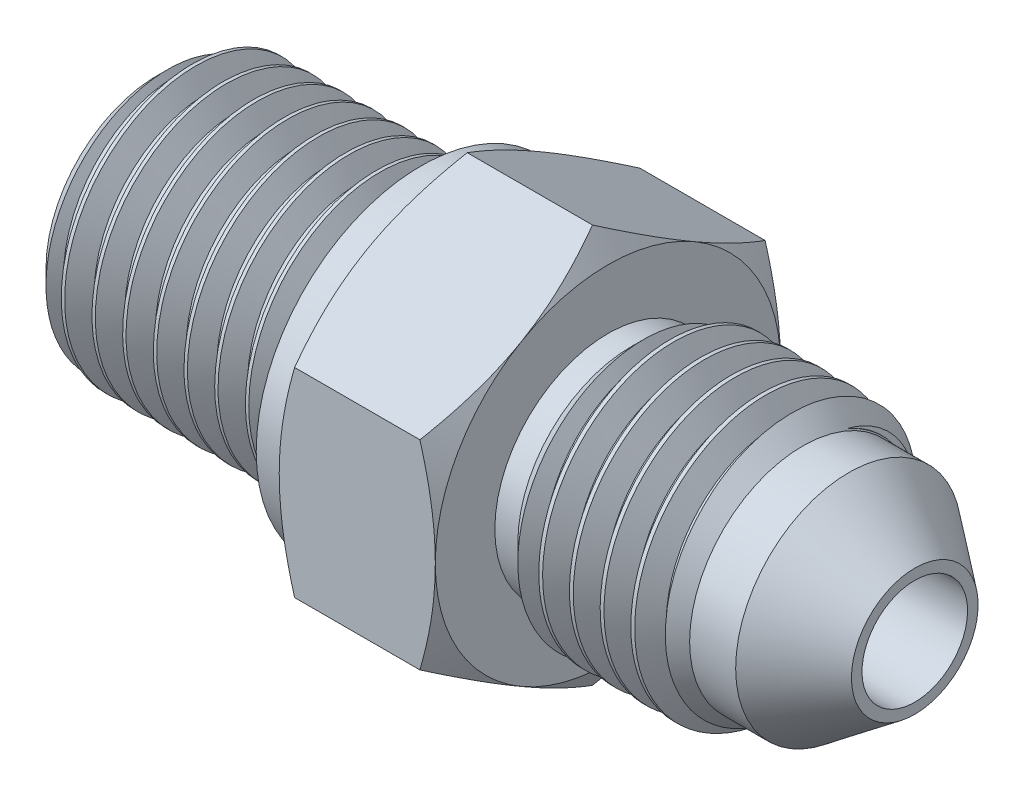
SolidWorks part; units mm, degrees
ref_plane "Front" through (0, 0, 0) normal (0, 0, 1) x (1, 0, 0)
ref_plane "Top" through (0, 0, 0) normal (0, 1, 0) x (1, 0, 0)
ref_plane "Right" through (0, 0, 0) normal (1, 0, 0) x (0, 0, -1)
sketch "Sketch6" plane through (0, 0, 0) normal (0, 0, 1) x (1, 0, 0)
  line L0 (-3.4836, 5.5562) -> (-3.4836, -5.5562) construction
  line L1 (15.6756, 5.5562) -> (15.6756, -5.5563) construction
  line L2 (-15.6756, 0) -> (15.6756, 0)
  line L4 (-15.6756, 0) -> (-15.6756, 5.5563)
  line L5 (-15.6756, 5.5563) -> (15.6756, 5.5562)
  line L6 (15.6756, 0) -> (15.6756, 5.5562)
  point P4 (2.9756, 0)
  point P6 (-3.4836, 0)
  dimension "Straight Dia" = 11.1125
  dimension "Length" = 31.3512
  dimension "L1" = 12.7
  dimension "Pipe OD" = 11.1125
  dimension "Pipe Thread Length" = 12.192
revolve "Revolve3" add sketch "Sketch6" angle 360 about L2
sketch "Sketch14" plane through (15.6756, 0, 0) normal (-1, 0, 0) x (0, 0, 1)
  circle A1 centre (0, 0) radius 5.5563
  circle A2 centre (0, 0) radius 5.5563
  dimension "D1" = 0
curve "Helix/Spiral1" pitch 1.27 height 13.97 turns 11 parameters "Pitch"=1.27
sketch "Sketch15" plane through (0, 0, 0) normal (0, 0, 1) x (1, 0, 0)
  line L0 (15.6756, 5.5563) -> (16.7869, 5.5562)
  line L1 (16.7869, 5.5562) -> (16.3106, 4.7314)
  line L2 (16.3106, 4.7314) -> (16.1519, 4.7314)
  line L3 (16.1519, 4.7314) -> (15.6756, 5.5563)
  line L4 (16.2312, 4.7314) -> (16.2312, 5.5563) construction
  line L5 (15.9137, 5.1438) -> (16.5487, 5.1438) construction
  dimension "D1" = 60
  dimension "D2" = 0.1588
  dimension "D3" = 0.635
sweep "Cut-Sweep1" cut profiles "Sketch15" path "Helix/Spiral1" align with end faces yes
ref_plane "Plane1" through (-3.4836, 0, 0) normal (1, 0, 0) x (0, 0, -1)
sketch "Sketch12" plane through (-3.4836, 0, 0) normal (1, 0, 0) x (0, 0, -1)
  line L1 (0, 8.2489) -> (-7.1437, 4.1244)
  line L2 (-7.1437, 4.1244) -> (-7.1437, -4.1244)
  line L3 (-7.1437, -4.1244) -> (0, -8.2489)
  line L4 (0, -8.2489) -> (7.1438, -4.1244)
  line L5 (7.1438, -4.1244) -> (7.1437, 4.1244)
  line L6 (7.1437, 4.1244) -> (0, 8.2489)
  circle A0 centre (0, 0) radius 7.1438 construction
  dimension "Hex" = 14.2875
extrude "Extrude1" add sketch "Sketch12" along normal up to vertex (6.4592 mm away) up to point (2.9756, 0, 0)
sketch "Sketch7" plane through (0, 0, 0) normal (0, 0, 1) x (1, 0, 0)
  line L0 (-15.6756, 0) -> (-15.6756, 2.1844)
  line L2 (-15.6756, 2.1844) -> (15.6756, 2.1844)
  line L4 (15.6756, 0) -> (15.6756, 5.5562) construction
  line L11 (15.6756, 2.1844) -> (15.6756, 0)
  line L12 (15.6756, 0) -> (-15.6756, 0)
  line L13 (-15.6756, 2.1844) -> (-15.6756, -2.1844) construction
  dimension "ID" = 4.3688
sketch "Sketch10" plane through (0, 0, 0) normal (0, 0, 1) x (1, 0, 0)
  line L0 (-15.6756, 5.5563) -> (15.6756, 5.5562) construction
  line L1 (15.6756, 5.5563) -> (16.7869, 5.5562) construction
  line L3 (2.9756, 8.2489) -> (2.9756, 4.1244) construction
  line L5 (0, 0) -> (-15.6756, 0) construction
  line L6 (4.8038, 5.5562) -> (2.9756, 5.5562)
  line L9 (2.9756, 4.6806) -> (2.9756, 5.5562)
  line L21 (15.6756, 5.5563) -> (10.1622, 5.5562)
  line L22 (10.1622, 5.5562) -> (11.0379, 4.6806)
  line L23 (11.0379, 4.6806) -> (12.9429, 4.6806)
  line L24 (12.9429, 4.6806) -> (15.6756, 2.6213)
  line L25 (15.6756, 2.6213) -> (15.6756, 5.5563)
  line L26 (3.9281, 4.6806) -> (2.9756, 4.6806)
  line L27 (4.8038, 5.5562) -> (3.9281, 4.6806)
  point P5 (8.4979, -5.5563)
  point P9 (-10.4026, -7.1438)
  point P24 (-10.4026, 0)
  dimension "D1" = 5.2426
  dimension "D2" = 37
  dimension "D3" = 1.905
  dimension "D5" = 45
  dimension "D4" = 0.9525
  dimension "D6" = 2.54
  dimension "D7" = 0.0508
revolve "Cut-Revolve6" cut sketch "Sketch10" angle 360 about L2
revolve "Cut-Revolve5" cut sketch "Sketch7" angle 360 about L12
sketch "Sketch13" plane through (0, 0, 0) normal (0, 0, 1) x (1, 0, 0)
  line L0 (-3.4836, 8.2489) -> (-3.4836, 7.1438)
  line L1 (-3.4836, 4.1244) -> (-3.4836, 8.2489) construction
  line L2 (-3.4836, 7.1438) -> (-2.8456, 8.2489)
  line L3 (-2.8456, 8.2489) -> (-3.4836, 8.2489)
  line L4 (2.3376, 8.2489) -> (2.9756, 7.1438)
  line L5 (2.9756, 8.2489) -> (2.9756, 4.1244) construction
  line L6 (2.9756, 7.1438) -> (2.9756, 8.2489)
  line L7 (2.9756, 8.2489) -> (2.3376, 8.2489)
  dimension "D2" = 30
revolve "Cut-Revolve7" cut sketch "Sketch13" angle 360 about L2
sketch "Sketch17" plane through (-15.6756, 0, 0) normal (-1, 0, 0) x (0, 0, 1)
  circle A0 centre (0, 0) radius 5.5563 construction
  circle A1 centre (0, 0) radius 5.5563
extrude "Cut-Extrude1" cut sketch "Sketch17" against normal up to vertex (12.192 mm away) up to point (-3.4836, 0, 0)
ref_plane "Plane2" through (-3.4836, 0, 0) normal (1, 0, 0) x (0, 0, -1)
sketch "Sketch19" plane through (-3.4836, 0, 0) normal (1, 0, 0) x (0, 0, -1)
  circle A0 centre (0, 0) radius 5.5562
extrude "Boss-Extrude1" add sketch "Sketch19" against normal up to vertex (12.192 mm away) separate body up to point (-15.6756, 0, 0)
sketch "Sketch20" plane through (-15.6756, 0, 0) normal (1, 0, 0) x (0, 0, -1)
  circle A1 centre (0, 0) radius 5.5562
  circle A2 centre (0, 0) radius 5.5562 construction
sketch "Sketch21" plane through (0, 0, 0) normal (0, 0, 1) x (1, 0, 0)
  line L0 (-16.7376, 5.4361) -> (-15.745, 5.4361) construction
  line L1 (-16.8763, 5.6764) -> (-16.2413, 4.5765) construction
  line L2 (-16.3614, 4.7846) -> (-16.1211, 4.7846)
  line L3 (-16.2413, 4.5765) -> (-15.6063, 5.6764) construction
  line L4 (-16.2413, 4.5765) -> (-16.1211, 4.7846) construction
  line L5 (-16.2413, 5.4361) -> (-16.2413, 5.6764) construction
  line L6 (-16.8763, 5.6764) -> (-15.6063, 5.6764) construction
  line L7 (-16.2413, 5.5562) -> (-15.6756, 5.5562) construction
  line L8 (-15.6063, 5.6764) -> (-16.8069, 5.5562)
  line L9 (-16.8069, 5.5562) -> (-16.3614, 4.7846)
  line L10 (-16.1211, 4.7846) -> (-15.6063, 5.6764)
  line L11 (-16.2413, 4.5765) -> (-16.2413, 4.7846) construction
  dimension "D2" = 0.2402
  dimension "D1" = 1.27
curve "Helix/Spiral2" pitch 1.27 height 13.462 radius 5.5562 centre (-15.6756, 0, 0) axis (1, 0, 0) start towards (0, 1, 0) parameters "Pitch"=1.27
chamfer "Chamfer1" distance 0.9525 angle 45 1 edges at (-15.6756, 0, -5.5562)
sketch "Sketch22" plane through (-3.4836, 0, 0) normal (1, 0, 0) x (0, 0, -1)
  circle A1 centre (0, 0) radius 5.5562
  circle A2 centre (0, 0) radius 5.5562
  dimension "D1" = 0
sweep "Cut-Sweep2" cut profiles "Sketch21" path "Helix/Spiral2" align with end faces yes
combine bodies "Combine1" operation type add bodies to combine 171 169
sketch "Sketch23" plane through (-15.6756, 0, 0) normal (-1, 0, 0) x (0, 0, 1)
  circle A2 centre (0, 0) radius 2.1844
  dimension "D1" = 4.3688
extrude "Cut-Extrude2" cut sketch "Sketch23" against normal up to vertex (12.192 mm away) up to point (-3.4836, 0, 0)
sketch "Sketch24" plane through (0, 0, 0) normal (0, 0, 1) x (1, 0, 0)
  line L0 (0, 0) -> (-17.0136, 0) construction
  line L1 (-4.7536, 6.8262) -> (-3.4836, 6.8262)
  line L2 (-4.7536, 6.8262) -> (-4.7536, 5.5562)
  line L3 (-4.7536, 5.5562) -> (-3.4836, 5.5562)
  line L4 (-3.4836, 6.8262) -> (-3.4836, 5.5562)
  line L5 (-3.4836, -5.5562) -> (-3.4836, 5.5562) construction
  line L6 (-16.2413, 5.5562) -> (-15.6756, 5.5562) construction
  dimension "D1" = 1.27
revolve "Revolve4" add sketch "Sketch24" angle 360 about L0
equation "\"D3@Helix/Spiral1\" = \"L1@Sketch6\"+\"Pitch@Helix/Spiral1\""
equation "\"D2@Sketch15\" = \"Pitch@Helix/Spiral1\"*.125"
equation "\"D3@Sketch15\" = \"Pitch@Helix/Spiral1\"*.5"
equation "\"D3@Sketch10\" = \"Pitch@Helix/Spiral1\"*1.5"
equation "\"D1@Sketch10\"=\"ID@Sketch7\"*1.2"
equation "\"D1@Sketch21\" = \"Pitch@Helix/Spiral2\""
equation "\"D3@Helix/Spiral2\" = \"Pipe Thread Length@Sketch6\"+\"Pitch@Helix/Spiral2\""
equation "\"D1@Chamfer1\" = \"Pitch@Helix/Spiral2\"*.75"
equation "\"D4@Sketch10\" = \"Pitch@Helix/Spiral1\"*.75"
equation "\"D6@Sketch10\" = \"Pitch@Helix/Spiral1\"*2"
equation "\"D1@Sketch24\"=\"Pitch@Helix/Spiral2\"*1."
